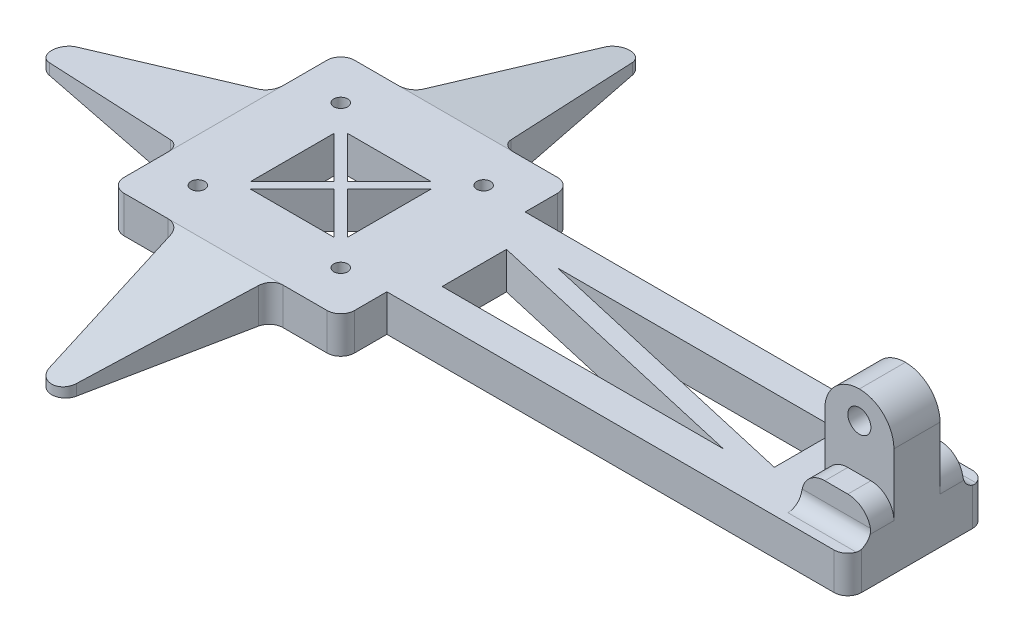
SolidWorks part; units mm, degrees
ref_plane "Front Plane" through (0, 0, 0) normal (0, 0, 1) x (1, 0, 0)
ref_plane "Top Plane" through (0, 0, 0) normal (0, 1, 0) x (1, 0, 0)
ref_plane "Right Plane" through (0, 0, 0) normal (1, 0, 0) x (0, 0, -1)
sketch "Sketch1" plane through (0, 0, 0) normal (0, 1, 0) x (1, 0, 0)
  line L0 (-10, 25) -> (0, 75)
  line L5 (0, 75) -> (10, 25)
  line L6 (-10, 25) -> (10, 25) construction
  line L7 (-10, 25) -> (-25, 25)
  line L8 (10, 25) -> (25, 25)
  line L9 (75, 0) -> (25, -10)
  line L10 (25, -10) -> (25, -25)
  line L11 (25, 10) -> (75, 0)
  line L12 (25, 10) -> (25, 25)
  line L13 (0, -75) -> (-10, -25)
  line L14 (-10, -25) -> (-25, -25)
  line L15 (10, -25) -> (0, -75)
  line L16 (10, -25) -> (25, -25)
  line L17 (-75, 0) -> (-25, 10)
  line L18 (-25, 10) -> (-25, 25)
  line L19 (-25, -10) -> (-75, 0)
  line L20 (-25, -10) -> (-25, -25)
  point P3 (0, 25)
  point P25 (0, 0)
  dimension "D1" = 20
  dimension "D2" = 50
  dimension "D3" = 25
  dimension "D4" = 50
  dimension "D5" = 4
extrude "Boss-Extrude1" add sketch "Sketch1" along normal blind 8
fillet "Fillet1" radius 3 4 edges at (75, 4, 0) (0, 4, -75) (-75, 4, 0) (0, 4, 75)
sketch "Sketch2" plane through (0, 0, 0) normal (1, 0, 0) x (0, 0, -1)
  line L0 (25, 8) -> (62.7029, 2)
  line L1 (62.7029, 0) -> (62.7029, 8) construction
  line L2 (62.7029, 2) -> (62.7029, 8)
  line L3 (62.7029, 8) -> (25, 8)
  line L4 (-10, 8) -> (-2.9417, 8) construction
  line L5 (25, 8) -> (25, 0) construction
  line L6 (60.2913, 0) -> (62.7029, 0) construction
  dimension "D1" = 2
extrude "Cut-Extrude1" cut sketch "Sketch2" against normal through all both and the other way through all
mirror "Mirror2" about plane through (0, 0, 0) normal (0, 0, 1) of "Cut-Extrude1"
sketch "Sketch3" plane through (0, 0, 0) normal (0, 0, 1) x (1, 0, 0)
  line L0 (-25, 8) -> (-62.7029, 2)
  line L1 (-62.7029, 8) -> (-62.7029, 0) construction
  line L2 (-62.7029, 2) -> (-62.7029, 8)
  line L3 (-62.7029, 8) -> (-25, 8)
  line L4 (-25, 8) -> (-25, 0) construction
  line L5 (-10, 8) -> (10, 8) construction
  line L6 (-62.7029, 0) -> (-60.2913, 0) construction
  dimension "D1" = 2
extrude "Cut-Extrude2" cut sketch "Sketch3" against normal through all both and the other way through all
fillet "Fillet2" radius 3 10 edges at (-10, 4, 25) (10, 4, 25) (-25, 4, 10) (-25, 4, -10) (-10, 4, -25) (10, 4, -25) (25, 4, -25) (25, 4, 25) (-25, 4, 25) (-25, 4, -25)
sketch "Sketch4" plane through (0, 8, 0) normal (0, 1, 0) x (1, 0, 0)
  line L1 (15.5, -15.5) -> (-15.5, -15.5) construction
  line L2 (15.5, -15.5) -> (15.5, 15.5) construction
  line L3 (15.5, 15.5) -> (-15.5, 15.5) construction
  line L4 (-15.5, -15.5) -> (-15.5, 15.5) construction
  line L5 (15.5, -15.5) -> (-15.5, 15.5) construction
  line L6 (15.5, 15.5) -> (-15.5, -15.5) construction
  circle A0 centre (-15.5, 15.5) radius 1.5
  circle A1 centre (15.5, 15.5) radius 1.5
  circle A2 centre (15.5, -15.5) radius 1.5
  circle A3 centre (-15.5, -15.5) radius 1.5
  point P0 (0, 0)
  dimension "D2" = 3
  dimension "D1" = 31
extrude "Cut-Extrude3" cut sketch "Sketch4" against normal through all
sketch "Sketch5" plane through (0, 0, 0) normal (0, -1, 0) x (1, 0, 0)
  circle A0 centre (15.5, -15.5) radius 2.5
  circle A1 centre (-15.5, -15.5) radius 2.5
  circle A2 centre (-15.5, 15.5) radius 2.5
  circle A3 centre (15.5, 15.5) radius 2.5
  dimension "D1" = 5
extrude "Cut-Extrude4" cut sketch "Sketch5" against normal blind 3
sketch "Sketch7" plane through (0, 8, 0) normal (0, 1, 0) x (1, 0, 0)
  line L0 (25, -22) -> (25, -10) construction
  line L1 (125, 15) -> (25, 15)
  line L2 (125, 15) -> (125, -15)
  line L3 (125, -15) -> (25, -15)
  line L4 (25, 15) -> (25, -15)
  line L5 (125, 15) -> (25, -15) construction
  line L6 (125, -15) -> (25, 15) construction
  point P0 (75, 0)
  point P11 (0, 0)
  dimension "D1" = 100
  dimension "D2" = 30
extrude "Boss-Extrude2" add sketch "Sketch7" against normal up to surface (8 mm away) up to face at (15.5, 0, 13)
sketch "Sketch8" plane through (0, 8, 0) normal (0, 1, 0) x (1, 0, 0)
  line L0 (125, -15) -> (125, 15) construction
  line L1 (110, 10) -> (125, 10)
  line L2 (110, 10) -> (110, -10)
  line L3 (110, -10) -> (125, -10)
  line L4 (125, 10) -> (125, -10)
  line L5 (110, 10) -> (125, -10) construction
  line L6 (110, -10) -> (125, 10) construction
  point P0 (117.5, 0)
  point P6 (0, 0)
  dimension "D1" = 15
  dimension "D2" = 20
extrude "Boss-Extrude3" add sketch "Sketch8" along normal blind 23
sketch "Sketch9" plane through (0, 0, 10) normal (0, 0, 1) x (1, 0, 0)
  line L0 (110, 31) -> (125, 31) construction
  circle A0 centre (117.5, 25) radius 2.5
  point P5 (117.5, 31)
  dimension "D2" = 5
  dimension "D1" = 6
extrude "Cut-Extrude5" cut sketch "Sketch9" against normal up to surface (20 mm away) up to face at (117.5, 19.5, -10)
fillet "Fillet3" radius 7.5 2 edges at (110, 31, 0) (125, 31, 0)
fillet "Fillet4" radius 3 2 edges at (117.5, 8, 10) (117.5, 8, -10)
fillet "Fillet5" radius 3 2 edges at (125, 4, 15) (125, 4, -15)
sketch "Sketch10" plane through (0, 8, 0) normal (0, 1, 0) x (1, 0, 0)
  line L0 (110, 13) -> (110, -13) construction
  line L1 (30, -8) -> (91.0243, -8)
  line L2 (30, -8) -> (30, 5.9484)
  line L3 (38.9757, 8) -> (100, 8)
  line L4 (100, -5.9484) -> (100, 8)
  line L5 (30, -8) -> (100, 8) construction
  line L6 (30, 8) -> (100, -8) construction
  line L7 (122, 15) -> (25, 15) construction
  line L8 (38.9757, 8) -> (100, -5.9484)
  line L9 (30, 5.9484) -> (91.0243, -8)
  line L10 (30, 8) -> (30, 5.9484) construction
  line L11 (30, 8) -> (38.9757, 8) construction
  line L12 (100, -8) -> (91.0243, -8) construction
  line L13 (100, -8) -> (100, -5.9484) construction
  line L14 (0, 0) -> (-11.5, -11.5) construction
  line L19 (11.5, -11.5) -> (-11.5, -11.5) construction
  line L20 (11.5, -11.5) -> (11.5, 11.5) construction
  line L21 (11.5, 11.5) -> (-11.5, 11.5) construction
  line L22 (-11.5, -11.5) -> (-11.5, 11.5) construction
  line L23 (0, 0) -> (-11.5, 11.5) construction
  line L24 (11.5, 11.5) -> (0, 0) construction
  line L25 (0, 0) -> (11.5, -11.5) construction
  line L26 (9.0858, 10.5) -> (0, 1.4142)
  line L27 (0, 1.4142) -> (-9.0858, 10.5)
  line L28 (9.0858, 10.5) -> (-9.0858, 10.5)
  line L29 (10.5, -9.0858) -> (1.4142, 0)
  line L30 (10.5, -9.0858) -> (10.5, 9.0858)
  line L31 (1.4142, 0) -> (10.5, 9.0858)
  line L32 (-9.0858, -10.5) -> (0, -1.4142)
  line L33 (-9.0858, -10.5) -> (9.0858, -10.5)
  line L34 (0, -1.4142) -> (9.0858, -10.5)
  line L35 (-10.5, 9.0858) -> (-1.4142, 0)
  line L36 (-10.5, 9.0858) -> (-10.5, -9.0858)
  line L37 (-1.4142, 0) -> (-10.5, -9.0858)
  point P0 (65, 0)
  point P5 (0, 0)
  point P15 (0, 0)
  point P16 (0, 0)
  point P37 (0, 0)
  dimension "D1" = 10
  dimension "D2" = 70
  dimension "D3" = 7
  dimension "D4" = 2
  dimension "D5" = 2
  dimension "D6" = 23
  dimension "D9" = 1
  dimension "D7" = 1
  dimension "D8" = 4
extrude "Cut-Extrude6" cut sketch "Sketch10" against normal through all
sketch "Sketch11" plane through (0, 0, 10) normal (0, 0, 1) x (1, 0, 0)
  line L4 (109, 25) -> (109, 32)
  line L5 (109, 32) -> (126, 32)
  line L6 (126, 32) -> (126, 25)
  line L7 (110, 23.5) -> (110, 11) construction
  arc A1 (109, 25) -> (126, 25) centre (117.5, 25) ccw
  dimension "D1" = 1
  dimension "D2" = 7
extrude "Cut-Extrude7" cut sketch "Sketch11" against normal blind 5
mirror "Mirror4" about plane through (0, 0, 0) normal (0, 0, 1) of "Cut-Extrude7"
sketch "Sketch12" plane through (0, 0, 10) normal (0, 0, 1) x (1, 0, 0)
  line L1 (110, 15) -> (125, 15)
  line L2 (110, 15) -> (110, 21)
  line L3 (110, 21) -> (125, 21)
  line L4 (125, 15) -> (125, 21)
  line L5 (110, 15) -> (125, 21) construction
  line L6 (110, 21) -> (125, 15) construction
  line L8 (110, 21) -> (110, 11) construction
  point P0 (117.5, 18)
  dimension "D1" = 6
extrude "Cut-Extrude8" cut sketch "Sketch12" against normal up to surface (5 mm away) up to face at (117.5, 23.7213, 5)
sketch "Sketch13" plane through (0, 0, -10) normal (0, 0, -1) x (-1, 0, 0)
  line L0 (-125, 21) -> (-125, 11) construction
  line L1 (-125, 15) -> (-110, 15)
  line L2 (-125, 15) -> (-125, 21)
  line L3 (-125, 21) -> (-110, 21)
  line L4 (-110, 15) -> (-110, 21)
  line L5 (-125, 15) -> (-110, 21) construction
  line L6 (-125, 21) -> (-110, 15) construction
  point P0 (-117.5, 18)
  dimension "D1" = 6
extrude "Cut-Extrude9" cut sketch "Sketch13" against normal up to surface (5 mm away) up to face at (117.5, 23.7213, -5)
fillet "Fillet6" radius 5 4 edges at (125, 15, -7.5) (110, 15, -7.5) (110, 15, 7.5) (125, 15, 7.5)
